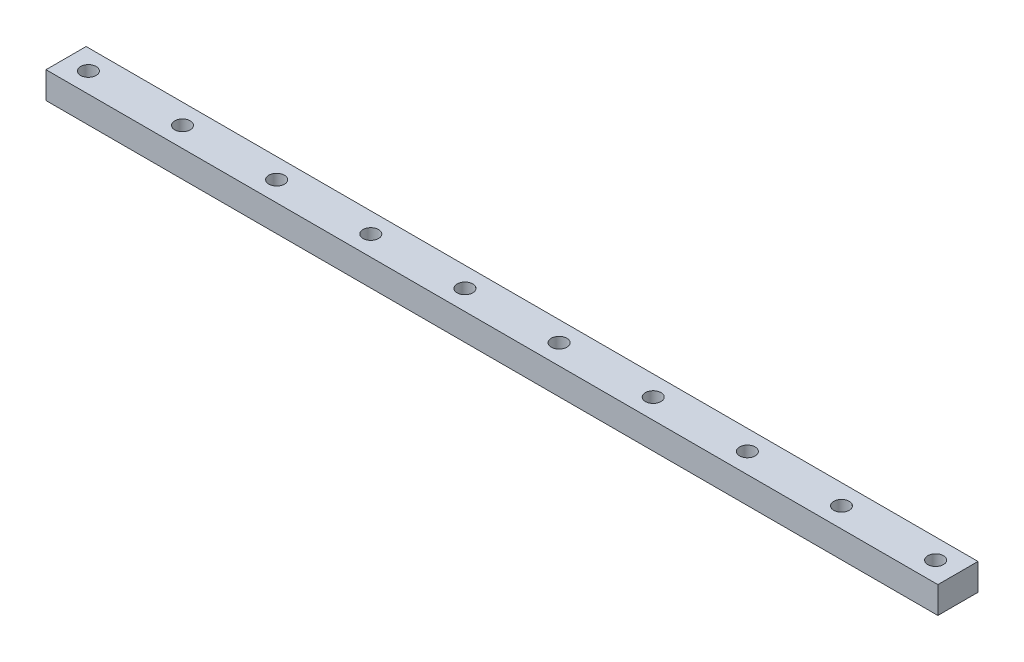
SolidWorks part; units mm, degrees
ref_plane "Front Plane" through (0, 0, 0) normal (0, 0, 1) x (1, 0, 0)
ref_plane "Top Plane" through (0, 0, 0) normal (0, 1, 0) x (1, 0, 0)
ref_plane "Right Plane" through (0, 0, 0) normal (1, 0, 0) x (0, 0, -1)
sketch "Sketch1" plane through (0, 0, 0) normal (0, 1, 0) x (1, 0, 0)
  line L1 (0, 0) -> (200, 0)
  line L2 (0, 0) -> (0, 9)
  line L3 (0, 9) -> (200, 9)
  line L4 (200, 0) -> (200, 9)
  dimension "D1" = 200
  dimension "D2" = 9
extrude "Boss-Extrude1" add sketch "Sketch1" along normal blind 6
sketch "Sketch2" plane through (0, 6, 0) normal (0, 1, 0) x (1, 0, 0)
  line L0 (0, 9) -> (0, 0) construction
  line L1 (0, 4.5) -> (35.1031, 4.5) construction
  circle A0 centre (5, 4.5) radius 1.75
  point P6 (5, 4.5)
  dimension "D1" = 3.5
  dimension "D2" = 5
extrude "Cut-Extrude1" cut sketch "Sketch2" against normal blind 6
pattern_linear "LPattern1" count 10 spacing 21.1111 along (1, 0, 0) of "Cut-Extrude1"
